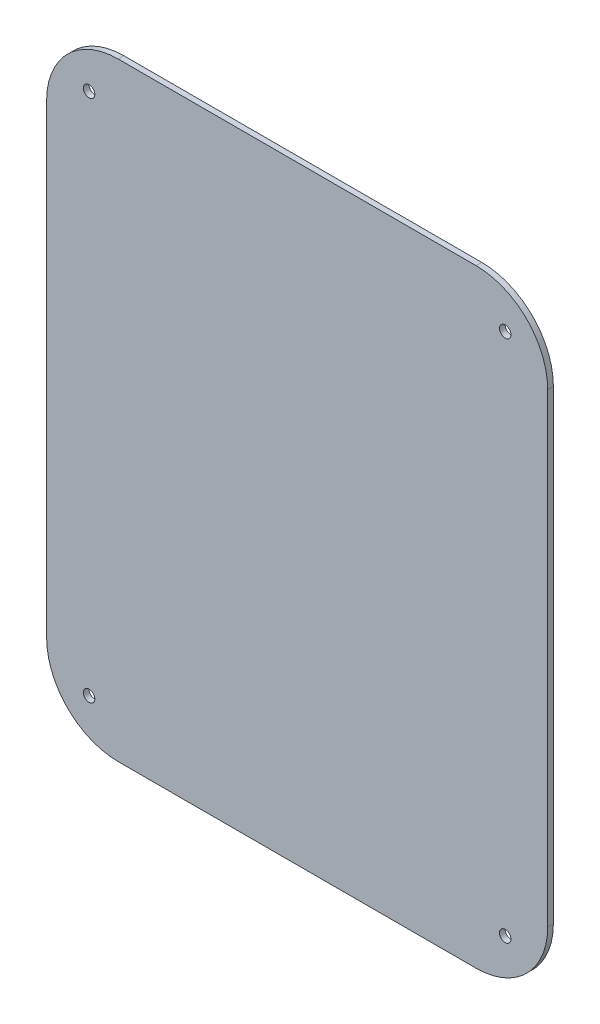
SolidWorks part; units mm, degrees
material "Acrylic (Medium-high impact)"
ref_plane "Front Plane" through (0, 0, 0) normal (0, 0, 1) x (1, 0, 0)
ref_plane "Top Plane" through (0, 0, 0) normal (0, 1, 0) x (1, 0, 0)
ref_plane "Right Plane" through (0, 0, 0) normal (1, 0, 0) x (0, 0, -1)
sketch "Sketch1" plane through (0, 0, 0) normal (0, 0, 1) x (1, 0, 0)
  line L0 (42.5, 123) -> (-57.5, 123) construction
  line L1 (62.5, -27) -> (62.5, 103) construction
  line L2 (-57.5, -47) -> (42.5, -47) construction
  line L3 (-77.5, 103) -> (-77.5, -27) construction
  line L4 (42.5, 123) -> (-57.5, 123)
  line L5 (62.5, -27) -> (62.5, 103)
  line L6 (-57.5, -47) -> (42.5, -47)
  line L7 (-77.5, 103) -> (-77.5, -27)
  arc A0 (62.5, 103) -> (42.5, 123) centre (42.5, 103) ccw construction
  arc A1 (42.5, -47) -> (62.5, -27) centre (42.5, -27) ccw construction
  arc A2 (-77.5, -27) -> (-57.5, -47) centre (-57.5, -27) ccw construction
  arc A3 (-57.5, 123) -> (-77.5, 103) centre (-57.5, 103) ccw construction
  arc A4 (62.5, 103) -> (42.5, 123) centre (42.5, 103) ccw
  arc A5 (42.5, -47) -> (62.5, -27) centre (42.5, -27) ccw
  arc A6 (-77.5, -27) -> (-57.5, -47) centre (-57.5, -27) ccw
  arc A7 (-57.5, 123) -> (-77.5, 103) centre (-57.5, 103) ccw
  circle A8 centre (-65.6317, -35.1317) radius 1.6 construction
  circle A9 centre (50.6317, -35.1317) radius 1.6 construction
  circle A10 centre (50.6317, 111.1317) radius 1.6 construction
  circle A11 centre (-65.6317, 111.1317) radius 1.6 construction
  circle A12 centre (-65.6317, -35.1317) radius 1.6
  circle A13 centre (50.6317, -35.1317) radius 1.6
  circle A14 centre (50.6317, 111.1317) radius 1.6
  circle A15 centre (-65.6317, 111.1317) radius 1.6
extrude "Boss-Extrude1" add sketch "Sketch1" along normal blind 1.5875
